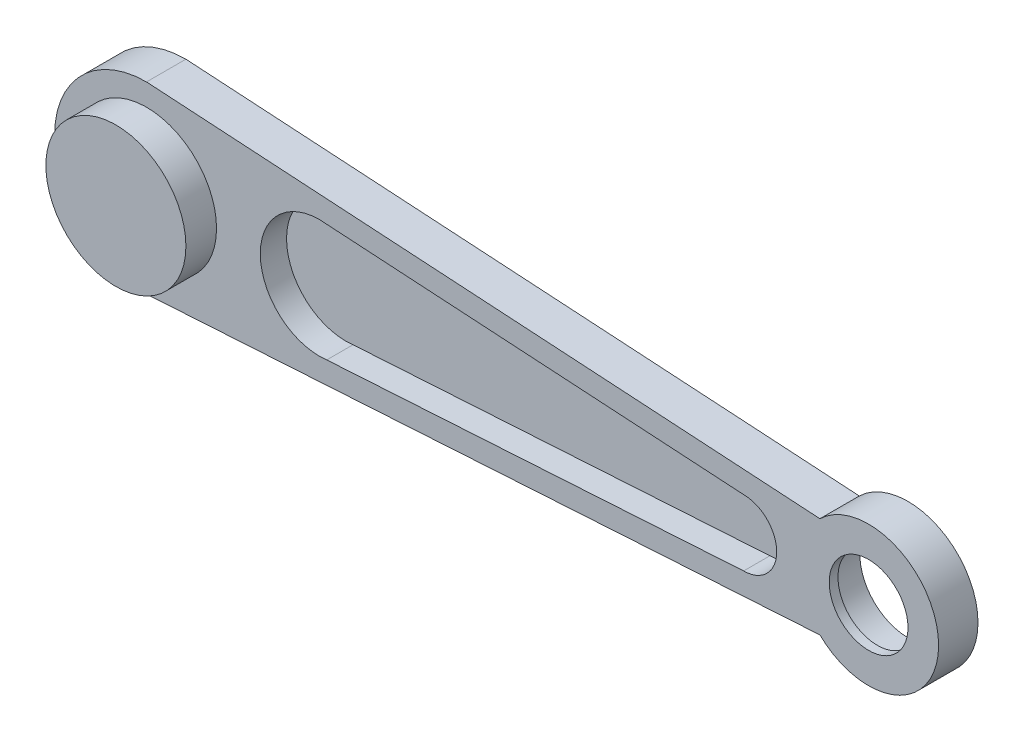
SolidWorks part; units mm, degrees
ref_plane "Front Plane" through (0, 0, 0) normal (0, 0, 1) x (1, 0, 0)
ref_plane "Top Plane" through (0, 0, 0) normal (0, 1, 0) x (1, 0, 0)
ref_plane "Right Plane" through (0, 0, 0) normal (1, 0, 0) x (0, 0, -1)
sketch "Sketch6" plane through (0, 0, 0) normal (0, 0, 1) x (1, 0, 0)
  line L0 (0, -21) -> (153.8757, -11.5)
  line L1 (39.5246, 13.5246) -> (136.4479, 7.5521)
  line L2 (0, 21) -> (153.8757, 11.5)
  line L3 (-58.5211, 0) -> (213.089, 0) construction
  line L4 (39.5246, -13.5246) -> (136.4479, -7.5521)
  circle A1 centre (165, 0) radius 11
  circle A2 centre (165, 0) radius 16
  circle A3 centre (0, 0) radius 16
  circle A4 centre (0, 0) radius 21
  circle A5 centre (165, 0) radius 9
  arc A6 (41.185, 13.4222) -> (41.185, -13.4222) centre (39.5246, 0) ccw
  arc A7 (136.4479, -7.5521) -> (136.4479, 7.5521) centre (136.4479, 0) ccw
  dimension "D1" = 22
  dimension "D2" = 5
  dimension "D3" = 165
  dimension "D4" = 32
  dimension "D5" = 5
  dimension "D6" = 23
  dimension "D7" = 2
  dimension "D8" = 5
  dimension "D9" = 5
  dimension "D10" = 5
  dimension "D12" = 42
  dimension "D11" = 5
extrude "Boss-Extrude2" add sketch "Sketch6" along normal blind 9 contours A4 L3 A2 L2 | A4 L3 A3 L2 | L3 A4 L0 A3 | L3 A3 | A3 L3 | L3 A4 L0 A2 | L3 A2 A1 | L3 A1 | A1 L3 | A2 L3 A1 | A6 L3 A7 L1 | L3 A6 L4 A7 region at (-14.5172, -14.5172, 0) region at (75.4942, -12.3056, 0) region at (-14.5172, 14.5172, 0) region at (150.5987, -6.1058, 0) region at (75.4942, 12.3056, 0) region at (0, 6.7906, 0) region at (0, -6.7906, 0) region at (178.5, 0.3578, 0) region at (79.5987, 5.3677, 0) region at (79.5987, -5.3677, 0) region at (165, -10.754, 0) region at (175, 0.246, 0)
extrude "Boss-Extrude3" add sketch "Sketch6<10>" along normal blind 16 contours A3
sketch "Sketch6<10>" plane through (0, 0, 0) normal (0, 0, 1) x (1, 0, 0) same geometry as "Sketch6"
extrude "Cut-Extrude2" cut sketch "Sketch6<13>" along normal up to next from offset 3 contours A6 L3 A7 L1 | L3 A6 L4 A7 region at (79.5987, 5.3677, 0) region at (79.5987, -5.3677, 0)
sketch "Sketch6<13>" plane through (0, 0, 0) normal (0, 0, 1) x (1, 0, 0) same geometry as "Sketch6"
extrude "Cut-Extrude5" cut sketch "Sketch6<20>" along normal offset from surface (7 mm away) 2 contours A1 up to face at (78.4689, 0, 9)
sketch "Sketch6<20>" plane through (0, 0, 0) normal (0, 0, 1) x (1, 0, 0) same geometry as "Sketch6"
